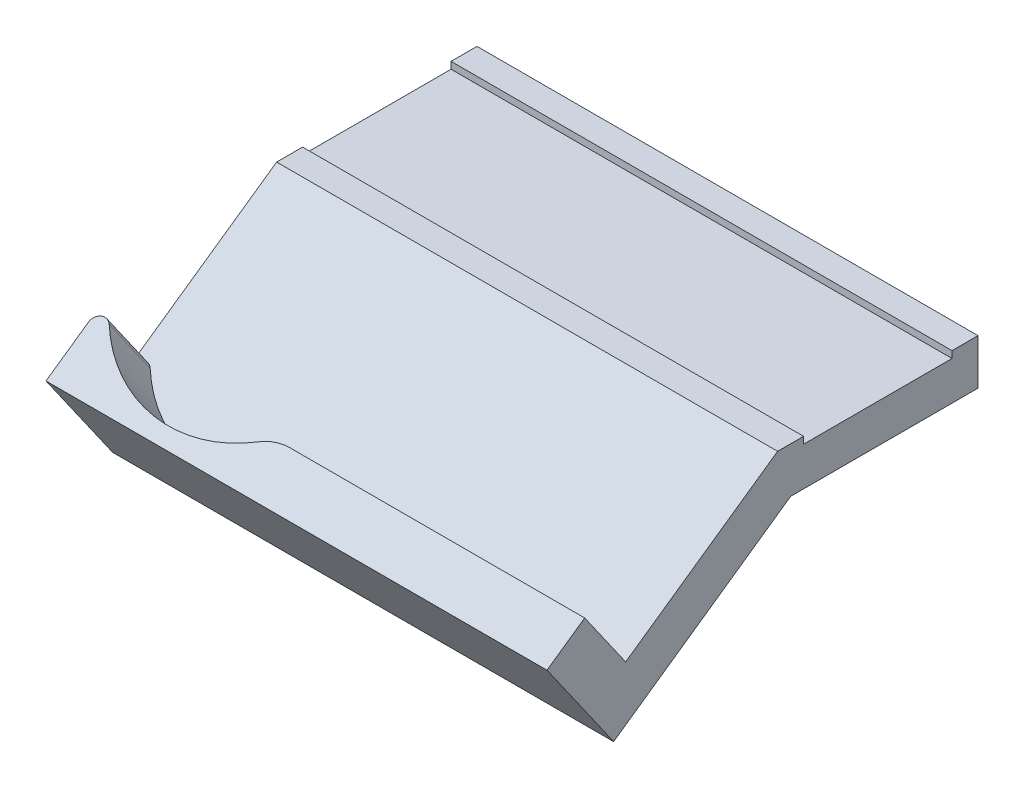
SolidWorks part; units mm, degrees
ref_plane "Front Plane" through (0, 0, 0) normal (0, 0, 1) x (1, 0, 0)
ref_plane "Top Plane" through (0, 0, 0) normal (0, 1, 0) x (1, 0, 0)
ref_plane "Right Plane" through (0, 0, 0) normal (1, 0, 0) x (0, 0, -1)
sketch "Sketch1" plane through (0, 0, 0) normal (0, 1, 0) x (1, 0, 0)
  line L1 (0, 29) -> (55, 29)
  line L2 (0, 29) -> (0, 0)
  line L3 (0, 0) -> (55, 0)
  line L4 (55, 29) -> (55, 0)
  dimension "D1" = 55
  dimension "D2" = 29
extrude "Boss-Extrude1" add sketch "Sketch1" along normal blind 50 contours L2 L3 L4 L1
sketch "Sketch4" plane through (55, 0, 0) normal (1, 0, 0) x (0, 0, -1)
  line L0 (29, 0) -> (0, 0) construction
  line L1 (-21.6788, 46.9576) -> (19.2788, 75.6364)
  line L2 (-21.6788, 46.9576) -> (7, 6)
  line L3 (7, 6) -> (47.9576, 34.6788)
  line L4 (19.2788, 75.6364) -> (47.9576, 34.6788)
  line L5 (0, 50) -> (0, 0) construction
  dimension "D1" = 50
  dimension "D2" = 50
  dimension "D3" = 6
  dimension "D4" = 7
  dimension "D5" = 35
extrude "Cut-Extrude1" cut sketch "Sketch4" against normal blind 50
sketch "Sketch5" plane through (55, 0, 0) normal (1, 0, 0) x (0, 0, -1)
  line L0 (0, 15.997) -> (0, 0) construction
  line L1 (-11.4273, 14.8824) -> (-3.2358, 20.6182)
  line L2 (-11.4273, 14.8824) -> (-5.6915, 6.6909)
  line L3 (-5.6915, 6.6909) -> (2.5, 12.4267)
  line L4 (-3.2358, 20.6182) -> (2.5, 12.4267)
  line L5 (0, 15.997) -> (7, 6) construction
  dimension "D1" = 10
  dimension "D2" = 10
  dimension "D3" = 2.5
extrude "Cut-Extrude2" cut sketch "Sketch5" against normal through all
sketch "Sketch12" plane through (55, 0, 0) normal (1, 0, 0) x (0, 0, -1)
  line L0 (2.5, 12.4267) -> (7, 6)
  line L1 (7, 6) -> (7.8192, 6.5736)
  line L2 (7, 6) -> (29, 21.4046) construction
  line L3 (7.8192, 6.5736) -> (3.3192, 13.0002)
  line L4 (3.3192, 13.0002) -> (2.5, 12.4267)
  dimension "D1" = 1
extrude "Boss-Extrude2" add sketch "Sketch12" against normal through all contours L3 L4 L0 L1
sketch "Sketch6" plane through (0, 0.7371, 0.5161) normal (0, 0.8192, 0.5736) x (1, 0, 0)
  line L0 (55, 6.1236) -> (0, 6.1236) construction
  line L3 (0, 52.4342) -> (0, 28.6788) construction
  circle A0 centre (12, 20.6236) radius 13.75
  dimension "D1" = 27.5
  dimension "D2" = 14.5
  dimension "D3" = 12
extrude "Cut-Extrude3" cut sketch "Sketch6" along normal through all
ref_axis "Axis2" through (12, 40.8781, 3.4464) along (0, -0.8192, -0.5736)
sketch "Sketch7" plane through (55, 0, 0) normal (1, 0, 0) x (0, 0, -1)
  line L0 (0, 10.6761) -> (6.3789, 15.1427)
  line L1 (21.8766, 16.4167) -> (10.8789, 8.716) construction
  line L2 (6.3789, 15.1427) -> (10.8789, 8.716)
  line L3 (10.8789, 8.716) -> (85.0856, 60.6761)
  line L4 (85.0856, 60.6761) -> (25.4084, 60.6761)
  line L5 (25.4084, 60.6761) -> (0, 60.6761)
  line L6 (0, 60.6761) -> (0, 10.6761)
  line L7 (10.8789, 8.716) -> (0, 24.2526) construction
  line L8 (7.8192, 6.5736) -> (29, 21.4046) construction
  dimension "D1" = 50
extrude "Cut-Extrude4" cut sketch "Sketch7" against normal through all contours L5 L6 L0 L2 L3 L4
sketch "Sketch8" plane through (0, 0, 0) normal (0, 1, 0) x (1, 0, 0)
  line L0 (12, -3.4464) -> (12, 9.8807) construction
  line L3 (55, 29) -> (0, 29) construction
  circle A0 centre (25.75, 30.5) radius 6
  dimension "D1" = 12
  dimension "D3" = 1.5
  dimension "D2" = 13.75
extrude "Cut-Extrude5" cut sketch "Sketch8" along normal through all contours A0
sketch "Sketch9" plane through (55, 0, 0) normal (1, 0, 0) x (0, 0, -1)
  line L0 (24.5, 18.2536) -> (29, 18.2536)
  line L1 (29, 21.4046) -> (29, 0) construction
  line L2 (29, 18.2536) -> (29, 21.4046)
  line L3 (29, 21.4046) -> (24.5, 18.2536)
extrude "Cut-Extrude6" cut sketch "Sketch9" against normal through all
sketch "Sketch10" plane through (0, 0, 0) normal (0, 1, 0) x (1, 0, 0)
  line L0 (0, 24.5) -> (25.75, 24.5) construction
  line L1 (55, 24.5) -> (0, 24.5)
  line L2 (55, 24.5) -> (55, 29)
  line L3 (55, 29) -> (0, 29)
  line L4 (0, 24.5) -> (0, 29)
  line L5 (0, 24.5) -> (0, 10.8789) construction
extrude "Cut-Extrude7" cut sketch "Sketch10" along normal through all
fillet "Fillet5" radius 1 1 edges at (0, 11.9293, -8.6289) tangent propagation no
fillet "Fillet6" radius 5 1 edges at (20.9387, 9.7869, -5.5692)
sketch "Sketch16" plane through (55, 0, 0) normal (1, 0, 0) x (0, 0, -1)
  line L0 (24.5, 12.2536) -> (7.3191, 0.2234)
  line L1 (24.5, 18.2536) -> (24.5, 0) construction
  line L2 (7.3191, 0.2234) -> (0, 10.6761)
  line L3 (0, 10.6761) -> (0, 0)
  line L4 (0, 0) -> (24.5, 0)
  line L5 (24.5, 0) -> (24.5, 12.2536)
  line L6 (7.8192, 6.5736) -> (24.5, 18.2536) construction
  dimension "D1" = 6
extrude "Cut-Extrude8" cut sketch "Sketch16" against normal through all
sketch "Sketch17" plane through (0, 0, -24.5) normal (0, 0, -1) x (-1, 0, 0)
  line L1 (-55, 18.2536) -> (0, 18.2536)
  line L2 (-55, 18.2536) -> (-55, 13.2536)
  line L3 (-55, 13.2536) -> (0, 13.2536)
  line L4 (0, 18.2536) -> (0, 13.2536)
  dimension "D1" = 5
extrude "Boss-Extrude4" add sketch "Sketch17" along normal blind 22
sketch "Sketch18" plane through (55, 0, 0) normal (1, 0, 0) x (0, 0, -1)
  line L0 (15.9095, 6.2385) -> (33.0689, 18.2536)
  line L1 (24.5, 12.2536) -> (7.3191, 0.2234) construction
  line L2 (46.5, 18.2536) -> (24.5, 18.2536) construction
  line L3 (33.0689, 18.2536) -> (24.5, 18.2536)
  line L4 (24.5, 18.2536) -> (13.0905, 10.2646)
  line L5 (7.8192, 6.5736) -> (24.5, 18.2536) construction
  line L6 (13.0905, 10.2646) -> (15.9095, 6.2385)
extrude "Boss-Extrude5" add sketch "Sketch18" against normal up to surface (55 mm away) contours L0 L3 L4 L6 up to face at (0, 11.8838, -21.8862)
sketch "Sketch19" plane through (0, 18.2536, 0) normal (0, 1, 0) x (1, 0, 0)
  line L0 (0, 46.5) -> (0, 24.5) construction
  line L1 (0, 43.65) -> (55, 43.65)
  line L2 (0, 43.65) -> (0, 27.35)
  line L3 (0, 27.35) -> (55, 27.35)
  line L4 (55, 43.65) -> (55, 27.35)
  line L5 (55, 46.5) -> (55, 24.5) construction
  point P8 (0, 35.5)
  dimension "D1" = 16.3
extrude "Cut-Extrude9" cut sketch "Sketch19" against normal blind 0.75
sketch "Sketch20" plane through (55, 0, 0) normal (1, 0, 0) x (0, 0, -1)
  line L0 (0, 10.6761) -> (-0.8192, 10.1026)
  line L1 (-0.8192, 10.1026) -> (6.4999, -0.3502)
  line L2 (6.4999, -0.3502) -> (7.3191, 0.2234)
  line L3 (7.3191, 0.2234) -> (0, 10.6761)
  line L4 (0, 10.6761) -> (3.3192, 13.0002) construction
  line L5 (25.9281, 13.2536) -> (7.3191, 0.2234) construction
  dimension "D1" = 1
extrude "Boss-Extrude6" add sketch "Sketch20" against normal up to surface (55 mm away) contours L1 L2 L3 L0 up to face at (0, 13.8096, -26.2658)
